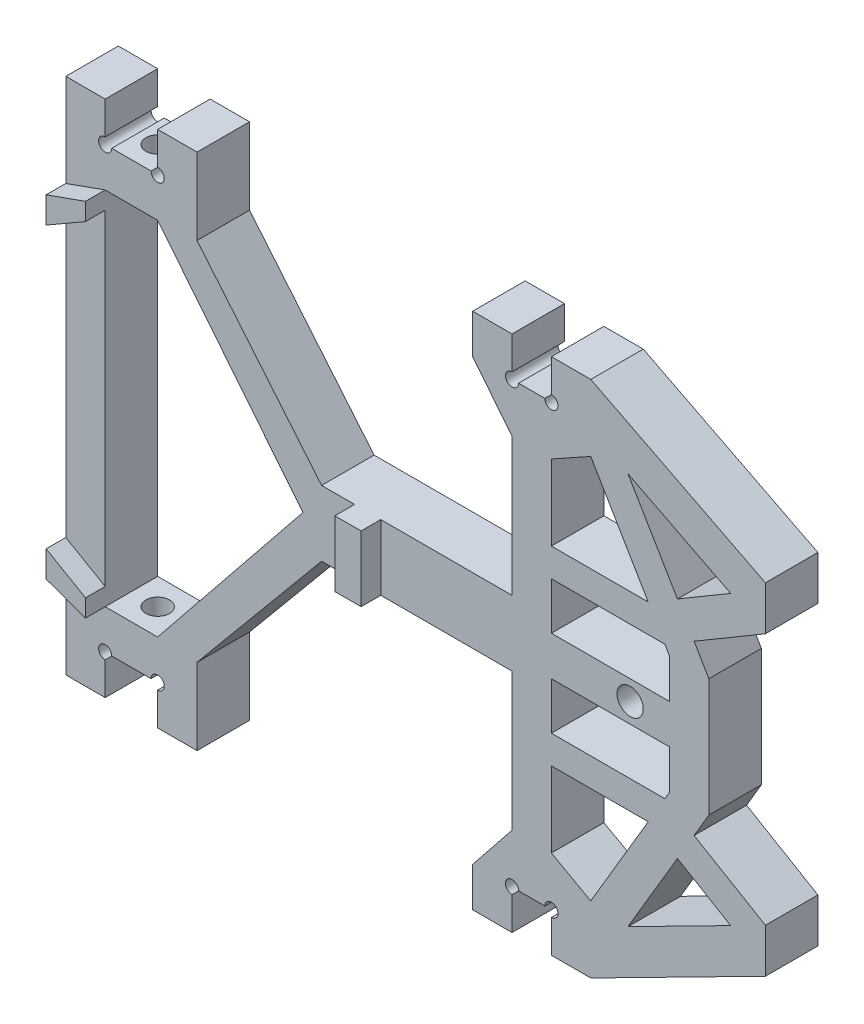
SolidWorks part; units mm, degrees
ref_plane "前视基准面" through (0, 0, 0) normal (0, 0, 1) x (1, 0, 0)
ref_plane "上视基准面" through (0, 0, 0) normal (0, 1, 0) x (1, 0, 0)
ref_plane "右视基准面" through (0, 0, 0) normal (1, 0, 0) x (0, 0, -1)
sketch "草图1" plane through (0, 0, 0) normal (0, 0, 1) x (1, 0, 0)
  line L12 (66, -1) -> (66, 1)
  line L13 (69, -5) -> (40, -19.75)
  line L14 (40, -19.75) -> (37, -19.75)
  line L15 (34.5, -16.75) -> (36.5, -16.75)
  line L16 (31, -16.75) -> (31, -19.75)
  line L17 (34, 13) -> (34, 2.5)
  line L18 (34, 13) -> (31, 16.75)
  line L19 (31, 19.75) -> (34, 19.75)
  line L20 (34, 19.75) -> (34, 17.25)
  line L21 (34.5, 16.75) -> (36.5, 16.75)
  line L22 (37, 13) -> (37, 1.5)
  line L23 (34, -19.75) -> (31, -19.75)
  line L24 (34, -13) -> (31, -16.75)
  line L25 (34, -19.75) -> (34, -17.25)
  line L26 (42.8383, -14.9406) -> (49, -4.5)
  line L27 (46, -1.5) -> (37, -1.5)
  line L28 (34, -2.5) -> (34, -13)
  line L29 (40, 14.6667) -> (46, 4.5)
  line L30 (46, 4.5) -> (46, 1.5)
  line L31 (63, 1.5) -> (64, 4.1774)
  line L32 (49, -1.5) -> (49, -4.5)
  line L33 (49, 4.5) -> (49, 1.5)
  line L34 (49, 1.5) -> (63, 1.5)
  line L35 (37, -17.25) -> (37, -19.75)
  line L36 (37, -1.5) -> (37, -13)
  line L37 (46, -1.5) -> (46, -4.5)
  line L38 (37, 19.75) -> (37, 17.25)
  line L39 (37, -13) -> (40, -14.6667)
  line L40 (46, -4.5) -> (40, -14.6667)
  line L41 (37, 13) -> (40, 14.6667)
  line L42 (37, 1.5) -> (46, 1.5)
  line L43 (42.8383, 14.9406) -> (64, 4.1774)
  line L44 (42.8383, -14.9406) -> (64, -4.1774)
  line L45 (49, 4.5) -> (42.8383, 14.9406)
  line L46 (66.5, 1.5) -> (69, 1.5)
  line L47 (69, 5) -> (69, 1.5)
  line L48 (63, -1.5) -> (49, -1.5)
  line L49 (37, 19.75) -> (40, 19.75)
  line L50 (40, 19.75) -> (69, 5)
  line L51 (31, 19.75) -> (31, 16.75)
  line L52 (69, -5) -> (69, -1.5)
  line L53 (66.5, -1.5) -> (69, -1.5)
  line L54 (63, -1.5) -> (64, -4.1774)
  line L55 (34, -2.5) -> (19.4926, -2.5)
  line L56 (34, 2.5) -> (19.4926, 2.5)
  line L57 (10, -13.9159) -> (19.4926, -2.5)
  line L58 (10, -19.75) -> (10, -13.9159)
  line L59 (10, -19.75) -> (7, -19.75)
  line L60 (7, -17.25) -> (7, -19.75)
  line L61 (3.5, -16.75) -> (6.5, -16.75)
  line L62 (3, -19.75) -> (3, -17.25)
  line L63 (3, -19.75) -> (0, -19.75)
  line L64 (3, -13.75) -> (7, -13.75)
  line L66 (18.0651, 0) -> (7, -13.75)
  line L67 (3, 13.75) -> (7, 13.75)
  line L68 (0, 19.75) -> (3, 19.75)
  line L69 (3, 19.75) -> (3, 17.25)
  line L70 (6.5, 16.75) -> (3.5, 16.75)
  line L71 (7, 19.75) -> (7, 17.25)
  line L72 (7, 19.75) -> (10, 19.75)
  line L73 (19.4926, 2.5) -> (10, 13.9159)
  line L74 (10, 19.75) -> (10, 13.9159)
  line L75 (7, 13.75) -> (18.0651, 0)
  line L78 (0, 19.75) -> (0, -19.75)
  line L81 (3, 13.75) -> (3, -13.75)
  arc A0 (66, -1) -> (66.5, -1.5) centre (66, -1.5) ccw
  arc A1 (37, -17.25) -> (36.5, -16.75) centre (37, -16.75) ccw
  arc A2 (34.5, -16.75) -> (34, -17.25) centre (34, -16.75) ccw
  arc A3 (34, 17.25) -> (34.5, 16.75) centre (34, 16.75) ccw
  arc A4 (36.5, 16.75) -> (37, 17.25) centre (37, 16.75) ccw
  arc A5 (66.5, 1.5) -> (66, 1) centre (66, 1.5) ccw
  arc A6 (7, -17.25) -> (6.5, -16.75) centre (7, -16.75) ccw
  arc A7 (3, 17.25) -> (3.5, 16.75) centre (3, 16.75) ccw
  arc A8 (6.5, 16.75) -> (7, 17.25) centre (7, 16.75) ccw
  arc A9 (3.5, -16.75) -> (3, -17.25) centre (3, -16.75) ccw
extrude "凸台-拉伸1" add sketch "草图1" along normal blind 4
sketch "草图2" plane through (0, -16.75, 0) normal (0, -1, 0) x (1, 0, 0)
  line L0 (3.5, 4) -> (6.5, 4) construction
  line L1 (3, 4) -> (3, 0) construction
  line L2 (7, 4) -> (7, 0) construction
  circle A0 centre (5, 2) radius 0.9
  dimension "D1" = 1.8
  dimension "D2" = 2
  dimension "D3" = 2
  dimension "D4" = 2
extrude "切除-拉伸1" cut sketch "草图2" against normal blind 52
sketch "草图3" plane through (0, 0, 4) normal (0, 0, 1) x (1, 0, 0)
  line L0 (3, 12.413) -> (3, 13.75)
  line L1 (3, 12.413) -> (0, 10.681)
  line L2 (0, 12.681) -> (0, 10.681)
  line L3 (0, 12.681) -> (3, 13.75)
  line L4 (24, -2.5) -> (24, 2.5)
  line L5 (24, -2.5) -> (22, -2.5)
  line L6 (22, 2.5) -> (22, -2.5)
  line L7 (22, 2.5) -> (24, 2.5)
  line L8 (3, -13.75) -> (3, -12.413)
  line L9 (3, -13.75) -> (0, -12.681)
  line L10 (0, -10.681) -> (0, -12.681)
  line L11 (0, -10.681) -> (3, -12.413)
extrude "凸台-拉伸2" add sketch "草图3" along normal blind 1.5
sketch "草图5" plane through (0, 0, 0) normal (0, 0, 1) x (1, 0, 0)
  line L0 (37, 7.25) -> (44.3771, 7.25)
  line L1 (37, 13) -> (37, 1.5) construction
  line L2 (46, 4.5) -> (40, 14.6667) construction
  line L3 (44.3771, 7.25) -> (50.664, 10.9603)
  line L4 (64, 4.1774) -> (42.8383, 14.9406) construction
  line L5 (37, 5.097) -> (45.6477, 5.097)
  line L6 (45.6477, 5.097) -> (53.3059, 9.6166)
  line L8 (42.8383, 14.9406) -> (49, 4.5) construction
  line L9 (37, 5.097) -> (37, 7.25)
  line L10 (53.3059, 9.6166) -> (50.664, 10.9603)
  line L11 (18.0651, 0) -> (31.8024, 0) construction
  line L12 (37, -5.097) -> (45.6477, -5.097)
  line L13 (37, -5.097) -> (37, -7.25)
  line L14 (37, -7.25) -> (44.3771, -7.25)
  line L15 (44.3771, -7.25) -> (50.664, -10.9603)
  line L16 (53.3059, -9.6166) -> (50.664, -10.9603)
  line L17 (45.6477, -5.097) -> (53.3059, -9.6166)
  dimension "D1" = 2.5
  dimension "D2" = 90
extrude "凸台-拉伸3" add sketch "草图5" along normal blind 4
sketch "草图6" plane through (0, 0, 4) normal (0, 0, 1) x (1, 0, 0)
  line L0 (53.3059, 9.6166) -> (53.3059, 18.7334)
  line L10 (37, 0) -> (71.9391, 0) construction
  line L11 (53.3059, -9.6166) -> (53.3059, -18.7334)
  line L12 (53.3059, 18.7334) -> (82.3391, 18.7334)
  line L13 (82.3391, 18.7334) -> (82.3391, -18.7334)
  line L14 (82.3391, -18.7334) -> (53.3059, -18.7334)
  line L15 (53.3059, 9.6166) -> (47.8727, 6.4101)
  line L16 (47.8727, 6.4101) -> (49, 4.5)
  line L17 (49, 4.5) -> (49, -4.5)
  line L18 (49, -4.5) -> (47.8727, -6.4101)
  line L19 (47.8727, -6.4101) -> (53.3059, -9.6166)
extrude "切除-拉伸3" cut sketch "草图6" against normal blind 4
ref_plane "基准面1" through (0, 0, 2) normal (0, 0, 1) x (1, 0, 0)
sketch "草图7" plane through (0, 0, 4) normal (0, 0, 1) x (1, 0, 0)
  line L0 (43, 0) -> (49, 0) construction
  line L1 (49, 4.5) -> (49, -4.5) construction
  circle A0 centre (43, 0) radius 1
  dimension "D1" = 2
  dimension "D2" = 6
extrude "切除-拉伸4" cut sketch "草图7" against normal blind 8
